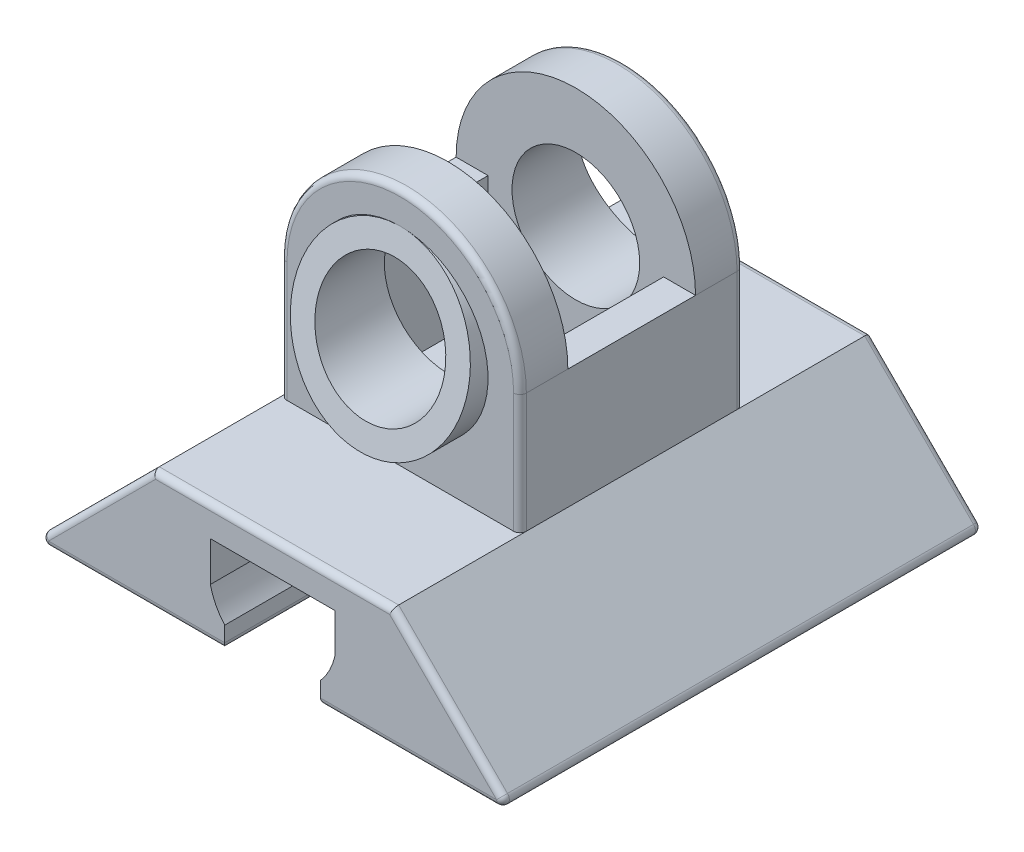
SolidWorks part; units mm, degrees
ref_plane "前视基准面" through (0, 0, 0) normal (0, 0, 1) x (1, 0, 0)
ref_plane "上视基准面" through (0, 0, 0) normal (0, 1, 0) x (1, 0, 0)
ref_plane "右视基准面" through (0, 0, 0) normal (1, 0, 0) x (0, 0, -1)
sketch "草图1" plane through (0, 0, 0) normal (0, 0, 1) x (1, 0, 0)
  line L2 (-3.75, 7.5) -> (-3.75, 3.75)
  line L3 (-3.75, 3.75) -> (3.75, 3.75)
  line L4 (3.75, 7.5) -> (3.75, 3.75)
  circle A0 centre (0, 7.5) radius 2
  arc A1 (3.75, 7.5) -> (-3.75, 7.5) centre (0, 7.5) ccw
extrude "凸台-拉伸1" add sketch "草图1" along normal blind 3.5 and the other way blind 3.5
sketch "草图2" plane through (0, 0, 0) normal (0, 0, 1) x (1, 0, 0)
  line L0 (-7.5, 0) -> (7.5, 0)
  line L1 (-3.75, 3.75) -> (-7.5, 0)
  line L2 (-3.75, 3.75) -> (3.75, 3.75)
  line L3 (3.75, 3.75) -> (7.5, 0)
extrude "凸台-拉伸2" add sketch "草图2" along normal blind 7.5 and the other way blind 7.5
sketch "草图3" plane through (0, 0, 0) normal (0, 0, 1) x (1, 0, 0)
  line L0 (3.75, 3.75) -> (-3.75, 3.75) construction
  line L1 (-2.75, 3.75) -> (2.75, 3.75)
  line L2 (-2.75, 3.75) -> (-2.75, 7.5)
  line L4 (2.75, 3.75) -> (2.75, 7.5)
  line L5 (2.75, 7.5) -> (3.75, 7.5)
  line L6 (3.75, 7.5) -> (3.75, 11.3873)
  line L7 (3.75, 11.3873) -> (-3.75, 11.3873)
  line L8 (-2.75, 7.5) -> (-3.75, 7.5)
  line L9 (-3.75, 7.5) -> (-3.75, 11.3873)
  arc A1 (3.75, 7.5) -> (-3.75, 7.5) centre (0, 7.5) ccw construction
extrude "切除-拉伸1" cut sketch "草图3" against normal blind 2 and the other way blind 2
sketch "草图4" plane through (0, 0, 3.5) normal (0, 0, 1) x (1, 0, 0)
  circle A0 centre (0, 7.5) radius 2
  circle A1 centre (0, 7.5) radius 2.75
extrude "凸台-拉伸3" add sketch "草图4" along normal blind 1.25
sketch "草图5" plane through (0, 0, -3.5) normal (0, 0, -1) x (-1, 0, 0)
  circle A0 centre (0, 7.5) radius 2
  circle A1 centre (0, 7.5) radius 2.75
extrude "凸台-拉伸4" add sketch "草图5" along normal blind 1.25
sketch "草图6" plane through (0, 0, 0) normal (1, 0, 0) x (0, 0, -1)
  line L0 (3.5, 10.25) -> (4.75, 4.75)
  line L5 (-4.75, 4.75) -> (-3.5, 10.25)
  line L6 (3.5, 10.25) -> (4.75, 10.25)
  line L7 (4.75, 10.25) -> (4.75, 4.75)
  line L8 (-3.5, 10.25) -> (-4.75, 10.25)
  line L9 (-4.75, 10.25) -> (-4.75, 4.75)
extrude "切除-拉伸2" cut sketch "草图6" against normal up to next and the other way up to next
sketch "草图7" plane through (0, 0, 7.5) normal (0, 0, 1) x (1, 0, 0)
  line L0 (-1.5, 0) -> (-1.5, 0.6771)
  line L1 (-7.5, 0) -> (7.5, 0) construction
  line L2 (1.5, 0) -> (1.5, 0.6771)
  line L3 (-1.95, 2.8) -> (1.95, 2.8)
  line L4 (-1.95, 2.8) -> (-1.95, 1.5556)
  line L5 (1.95, 2.8) -> (1.95, 1.5556)
  line L6 (-1.5, 0) -> (1.5, 0)
  arc A1 (1.5, 0.6771) -> (1.95, 1.5556) centre (0, 2) ccw
  arc A2 (-1.95, 1.5556) -> (-1.5, 0.6771) centre (0, 2) ccw
extrude "切除-拉伸3" cut sketch "草图7" against normal blind 9.45
fillet "圆角1" radius 0.2 14 edges at (4.5, 0, 7.5) (7.5, 0, 0) (0, 0, -7.5) (-7.5, 0, 0) (-4.5, 0, 7.5) (-1.5, 0, 2.775) (0, 0, -1.95) (1.5, 0, 2.775) (5.625, 1.875, -7.5) (0, 3.75, -7.5) (-5.625, 1.875, -7.5) (0, 3.75, 7.5) (-5.625, 1.875, 7.5) (5.625, 1.875, 7.5)
fillet "圆角2" radius 0.2 6 edges at (0, 11.25, -3.5) (0, 11.25, 3.5)
